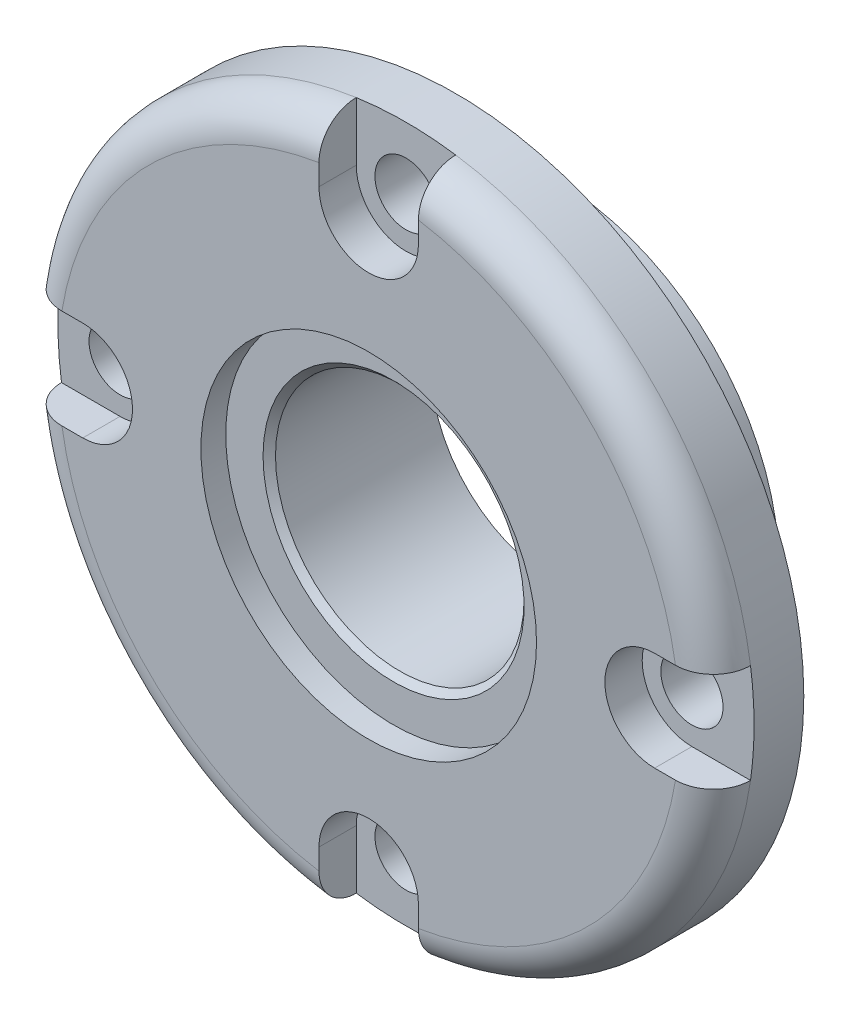
SolidWorks part; units mm, degrees
ref_plane "Front Plane" through (0, 0, 0) normal (1, 0, 0) x (0, 1, 0)
ref_plane "Top Plane" through (0, 0, 0) normal (0, 0, 1) x (0, 1, 0)
ref_plane "Right Plane" through (0, 0, 0) normal (0, 1, 0) x (-1, 0, 0)
sketch "Sketch2" plane through (0, 0, 0) normal (0, 1, 0) x (-1, 0, 0)
  line L0 (0, 28.0293) -> (0, -29.2447) construction
  line L1 (-40.5627, 0) -> (52.1087, 0) construction
  line L2 (13.5, 7) -> (28, 7)
  line L3 (28, 7) -> (28, 0)
  line L4 (28, 0) -> (18, 0)
  line L5 (18, 0) -> (18, -8)
  line L6 (18, -8) -> (10, -8)
  line L7 (10, -8) -> (10, 5)
  line L8 (10, 5) -> (13.5, 5)
  line L9 (13.5, 5) -> (13.5, 7)
  point P5 (18, -4)
  dimension "D1" = 15
  dimension "D2" = 8
  dimension "D3" = 28
  dimension "D4" = 27
  dimension "D5" = 20
  dimension "D6" = 36
  dimension "D7" = 2
revolve "Revolve1" add sketch "Sketch2" angle 360 about L0
fillet "Fillet1" radius 3 1 edges at (28, 0, 7)
chamfer "Chamfer1" distance 0.5 angle 45 1 edges at (10, 0, 5)
sketch "Sketch3" plane through (0, 0, 7) normal (0, 0, 1) x (1, 0, 0)
  line L0 (-4, 23) -> (-4, 27.7128)
  line L1 (4, 23) -> (4, 27.7128)
  line L2 (23, -4) -> (27.7128, -4)
  line L3 (23, 4) -> (27.7128, 4)
  line L4 (-4, -23) -> (-4, -27.7128)
  line L5 (4, -23) -> (4, -27.7128)
  line L6 (-23, 4) -> (-27.7128, 4)
  line L7 (-23, -4) -> (-27.7128, -4)
  arc A0 (4, 27.7128) -> (-4, 27.7128) centre (0, 0) ccw
  circle A1 centre (0, 0) radius 23 construction
  circle A2 centre (0, 23) radius 2.5
  arc A3 (-4, 23) -> (4, 23) centre (0, 23) ccw
  arc A4 (23, 4) -> (23, -4) centre (23, 0) ccw
  circle A5 centre (23, 0) radius 2.5
  arc A6 (27.7128, -4) -> (27.7128, 4) centre (0, 0) ccw
  arc A7 (4, -23) -> (-4, -23) centre (0, -23) ccw
  circle A8 centre (0, -23) radius 2.5
  arc A9 (-4, -27.7128) -> (4, -27.7128) centre (0, 0) ccw
  arc A10 (-23, -4) -> (-23, 4) centre (-23, 0) ccw
  circle A11 centre (-23, 0) radius 2.5
  arc A12 (-27.7128, 4) -> (-27.7128, -4) centre (0, 0) ccw
  circle A13 centre (0, 0) radius 13.5 construction
  circle M5 centre (0, 0) radius 25
  dimension "D1" = 56
  dimension "D2" = 46
  dimension "D3" = 8
  dimension "D4" = 5
  dimension "D5" = 4
extrude "Cut-Extrude2" cut sketch "Sketch3" against normal blind 3 contours A8 M5 | A8 L5 A7 L4 M5 | A8 M5 | L4 A9 L5 A8 M5 | A11 M5 | A11 M5 | A11 L7 A10 L6 M5 | L6 A12 L7 A11 M5 | A2 L1 A0 L0 M5 | L0 A3 L1 A2 M5 | A2 M5 | A2 M5 | L2 A6 L3 A5 M5 | A5 L3 A4 L2 M5 | A5 M5 | A5 M5 region at (-3.9003, 23.839, 7) region at (0, 26.4544, 7) region at (0, 22.8737, 7) region at (0, 25.1921, 7) region at (-26.4544, 0, 7) region at (-23.839, 3.9003, 7) region at (-25.1921, 0, 7) region at (-22.8737, 0, 7) region at (24.7453, 2.7738, 7) region at (26.4544, 0, 7) region at (22.8737, 0, 7) region at (25.1921, 0, 7) region at (0, -26.4544, 7) region at (-3.9003, -23.839, 7) region at (0, -25.1921, 7) region at (0, -22.8737, 7)
extrude "Cut-Extrude3" cut sketch "Sketch3<4>" against normal through all both and the other way through all contours A11 M5 | A8 | A11 | A5 | A2 region at (-22.8737, 0, 7)
sketch "Sketch3<4>" plane through (0, 0, 7) normal (0, 0, 1) x (1, 0, 0) same geometry as "Sketch3"
